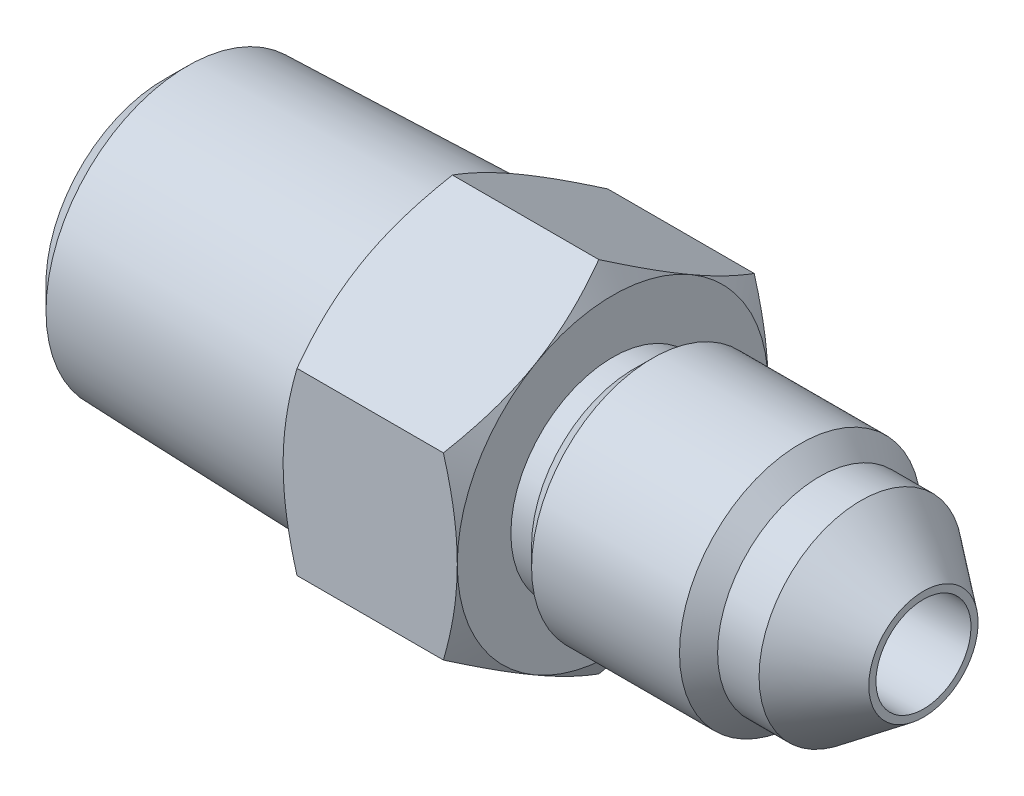
SolidWorks part; units mm, degrees
ref_plane "Front" through (0, 0, 0) normal (0, 0, 1) x (1, 0, 0)
ref_plane "Top" through (0, 0, 0) normal (0, 1, 0) x (1, 0, 0)
ref_plane "Right" through (0, 0, 0) normal (1, 0, 0) x (0, 0, -1)
sketch "Sketch6" plane through (0, 0, 0) normal (0, 0, 1) x (1, 0, 0)
  line L0 (-4.8311, 6.858) -> (-4.8311, -6.858) construction
  line L1 (17.4625, 5.5563) -> (17.4625, -5.5562) construction
  line L2 (-17.4625, 0) -> (17.4625, 0)
  line L4 (-17.4625, 0) -> (-17.4625, 5.5563)
  line L5 (-17.4625, 5.5563) -> (17.4625, 5.5563)
  line L6 (17.4625, 0) -> (17.4625, 5.5563)
  point P4 (3.175, 0)
  point P6 (-4.8311, 0)
  dimension "Straight Dia" = 11.1125
  dimension "Length" = 34.925
  dimension "L1" = 14.2875
  dimension "Pipe OD" = 13.716
  dimension "Pipe Thread Length" = 12.6314
revolve "Revolve3" add sketch "Sketch6" angle 360 about L2
sketch "Sketch14" plane through (17.4625, 0, 0) normal (-1, 0, 0) x (0, 0, 1)
  circle A1 centre (0, 0) radius 5.5563
  circle A2 centre (0, 0) radius 5.5563
  dimension "D1" = 0
curve "Helix/Spiral1" pitch 1.27 height 15.5575 turns 12.25 parameters "Pitch"=1.27
sketch "Sketch15" plane through (0, 0, 0) normal (0, 0, 1) x (1, 0, 0)
  line L0 (17.4625, 5.5563) -> (18.5738, 5.5563)
  line L1 (18.5738, 5.5563) -> (18.0975, 4.7314)
  line L2 (18.0975, 4.7314) -> (17.9387, 4.7314)
  line L3 (17.9387, 4.7314) -> (17.4625, 5.5563)
  line L4 (18.0181, 4.7314) -> (18.0181, 5.5563) construction
  line L5 (17.7006, 5.1438) -> (18.3356, 5.1438) construction
  dimension "D1" = 60
  dimension "D2" = 0.1588
  dimension "D3" = 0.635
sweep "Cut-Sweep1" [suppressed] cut profiles "Sketch15" path "Helix/Spiral1"
ref_plane "Plane1" through (-4.8311, 0, 0) normal (1, 0, 0) x (0, 0, -1)
sketch "Sketch12" plane through (-4.8311, 0, 0) normal (1, 0, 0) x (0, 0, -1)
  line L1 (0, 8.2489) -> (-7.1437, 4.1244)
  line L2 (-7.1437, 4.1244) -> (-7.1437, -4.1244)
  line L3 (-7.1437, -4.1244) -> (0, -8.2489)
  line L4 (0, -8.2489) -> (7.1437, -4.1244)
  line L5 (7.1437, -4.1244) -> (7.1437, 4.1244)
  line L6 (7.1437, 4.1244) -> (0, 8.2489)
  circle A0 centre (0, 0) radius 7.1438 construction
  dimension "Hex" = 14.2875
extrude "Extrude1" add sketch "Sketch12" along normal up to vertex (8.0061 mm away) up to point (3.175, 0, 0)
sketch "Sketch7" plane through (0, 0, 0) normal (0, 0, 1) x (1, 0, 0)
  line L0 (-17.4625, 0) -> (-17.4625, 2.1844)
  line L2 (-17.4625, 2.1844) -> (17.4625, 2.1844)
  line L4 (17.4625, 0) -> (17.4625, 5.5563) construction
  line L11 (17.4625, 2.1844) -> (17.4625, 0)
  line L12 (17.4625, 0) -> (-17.4625, 0)
  line L13 (-17.4625, 2.1844) -> (-17.4625, -2.1844) construction
  dimension "ID" = 4.3688
sketch "Sketch10" plane through (0, 0, 0) normal (0, 0, 1) x (1, 0, 0)
  line L0 (-17.4625, 5.5563) -> (17.4625, 5.5563) construction
  line L1 (17.4625, 5.5563) -> (18.5738, 5.5563) construction
  line L3 (3.175, 8.2489) -> (3.175, 4.1244) construction
  line L5 (0, 0) -> (-17.4625, 0) construction
  line L6 (5.0032, 5.5562) -> (3.175, 5.5562)
  line L9 (3.175, 4.6806) -> (3.175, 5.5562)
  line L21 (17.4625, 5.5563) -> (11.8041, 5.5563)
  line L22 (11.8041, 5.5563) -> (12.6798, 4.6806)
  line L23 (12.6798, 4.6806) -> (14.5848, 4.6806)
  line L24 (14.5848, 4.6806) -> (17.4625, 2.5121)
  line L25 (17.4625, 2.5121) -> (17.4625, 5.5563)
  line L26 (4.1275, 4.6806) -> (3.175, 4.6806)
  line L27 (5.0032, 5.5562) -> (4.1275, 4.6806)
  point P5 (10.1398, -5.5562)
  point P9 (-10.4026, -7.1438)
  point P24 (-10.4026, 0)
  dimension "D1" = 5.0241
  dimension "D2" = 37
  dimension "D3" = 1.905
  dimension "D5" = 45
  dimension "D4" = 0.9525
  dimension "D6" = 2.54
  dimension "D7" = 0.0508
revolve "Cut-Revolve6" cut sketch "Sketch10" angle 360 about L2
revolve "Cut-Revolve5" cut sketch "Sketch7" angle 360 about L12
sketch "Sketch13" plane through (0, 0, 0) normal (0, 0, 1) x (1, 0, 0)
  line L0 (-4.8311, 8.2489) -> (-4.8311, 7.1438)
  line L1 (-4.8311, 4.1244) -> (-4.8311, 8.2489) construction
  line L2 (-4.8311, 7.1438) -> (-4.193, 8.2489)
  line L3 (-4.193, 8.2489) -> (-4.8311, 8.2489)
  line L4 (2.5369, 8.2489) -> (3.175, 7.1438)
  line L5 (3.175, 8.2489) -> (3.175, 4.1244) construction
  line L6 (3.175, 7.1438) -> (3.175, 8.2489)
  line L7 (3.175, 8.2489) -> (2.5369, 8.2489)
  dimension "D2" = 30
revolve "Cut-Revolve7" cut sketch "Sketch13" angle 360 about L2
sketch "Sketch17" plane through (-17.4625, 0, 0) normal (-1, 0, 0) x (0, 0, 1)
  circle A0 centre (0, 0) radius 5.5563 construction
  circle A1 centre (0, 0) radius 5.5563
extrude "Cut-Extrude1" cut sketch "Sketch17" against normal up to vertex (12.6314 mm away) up to point (-4.8311, 0, 0)
ref_plane "Plane2" through (-4.8311, 0, 0) normal (1, 0, 0) x (0, 0, -1)
sketch "Sketch19" plane through (-4.8311, 0, 0) normal (1, 0, 0) x (0, 0, -1)
  circle A0 centre (0, 0) radius 6.858
extrude "Boss-Extrude1" add sketch "Sketch19" against normal up to vertex (12.6314 mm away) draft 1.75 separate body up to point (-17.4625, 0, 0)
sketch "Sketch20" plane through (-17.4625, 0, 0) normal (1, 0, 0) x (0, 0, -1)
  circle A1 centre (0, 0) radius 6.4721
  circle A2 centre (0, 0) radius 6.4721 construction
sketch "Sketch21" plane through (0, 0, 0) normal (0, 0, 1) x (1, 0, 0)
  line L0 (-18.6656, 6.352) -> (-17.5318, 6.352) construction
  line L1 (-18.8043, 6.5922) -> (-18.0987, 5.3701) construction
  line L2 (-18.2188, 5.5782) -> (-17.9786, 5.5782)
  line L3 (-18.0987, 5.3701) -> (-17.3932, 6.5922) construction
  line L4 (-18.0987, 5.3701) -> (-17.9786, 5.5782) construction
  line L5 (-18.0987, 6.352) -> (-18.0987, 6.5922) construction
  line L6 (-18.8043, 6.5922) -> (-17.3932, 6.5922) construction
  line L7 (-18.0987, 6.4721) -> (-17.4625, 6.4721) construction
  line L8 (-17.3932, 6.5922) -> (-18.7349, 6.4721)
  line L9 (-18.7349, 6.4721) -> (-18.2188, 5.5782)
  line L10 (-17.9786, 5.5782) -> (-17.3932, 6.5922)
  line L11 (-18.0987, 5.3701) -> (-18.0987, 5.5782) construction
  dimension "D2" = 0.2402
  dimension "D1" = 1.4111
curve "Helix/Spiral2" parameters "Pitch"=1.4111
chamfer "Chamfer1" distance 1.0583 angle 45 1 edges at (-17.4625, 0, -6.4721) first distance on face at (-17.4625, 0, -6.4721)
sketch "Sketch22" plane through (-4.8311, 0, 0) normal (1, 0, 0) x (0, 0, -1)
  circle A1 centre (0, 0) radius 6.858
  circle A2 centre (0, 0) radius 6.858
  dimension "D1" = 0
sweep "Cut-Sweep2" [suppressed] cut profiles "Sketch21" path "Helix/Spiral2"
extrude "Boss-Extrude3" add sketch "Sketch22" against normal up to vertex (12.6314 mm away) draft 15 up to point (-17.4625, 5.5563, 0)
combine bodies "Combine1" operation type add bodies to combine 173 169
sketch "Sketch23" plane through (-17.4625, 0, 0) normal (-1, 0, 0) x (0, 0, 1)
  circle A1 centre (0, 0) radius 4.6517
  circle A2 centre (0, 0) radius 4.6517
  dimension "D1" = 0.762
extrude "Cut-Extrude2" cut sketch "Sketch23" against normal up to vertex (12.6314 mm away) up to point (-4.8311, 0, 0)
other "CPoint1" parameters "Diameter"=6.35, "StubLength"=19.05
ref_axis "Axis1" through (27.4625, 0, 0) along (-1, 0, 0)
equation "\"D3@Helix/Spiral1\" = \"L1@Sketch6\"+\"Pitch@Helix/Spiral1\""
equation "\"D2@Sketch15\" = \"Pitch@Helix/Spiral1\"*.125"
equation "\"D3@Sketch15\" = \"Pitch@Helix/Spiral1\"*.5"
equation "\"D3@Sketch10\" = \"Pitch@Helix/Spiral1\"*1.5"
equation "\"D1@Sketch10\" = \"ID@Sketch7\"*1.15"
equation "\"D1@Sketch21\" = \"Pitch@Helix/Spiral2\""
equation "\"D3@Helix/Spiral2\" = \"Pipe Thread Length@Sketch6\"+\"Pitch@Helix/Spiral2\""
equation "\"D1@Chamfer1\" = \"Pitch@Helix/Spiral2\"*.75"
equation "\"D4@Sketch10\" = \"Pitch@Helix/Spiral1\"*.75"
equation "\"D6@Sketch10\" = \"Pitch@Helix/Spiral1\"*2"
